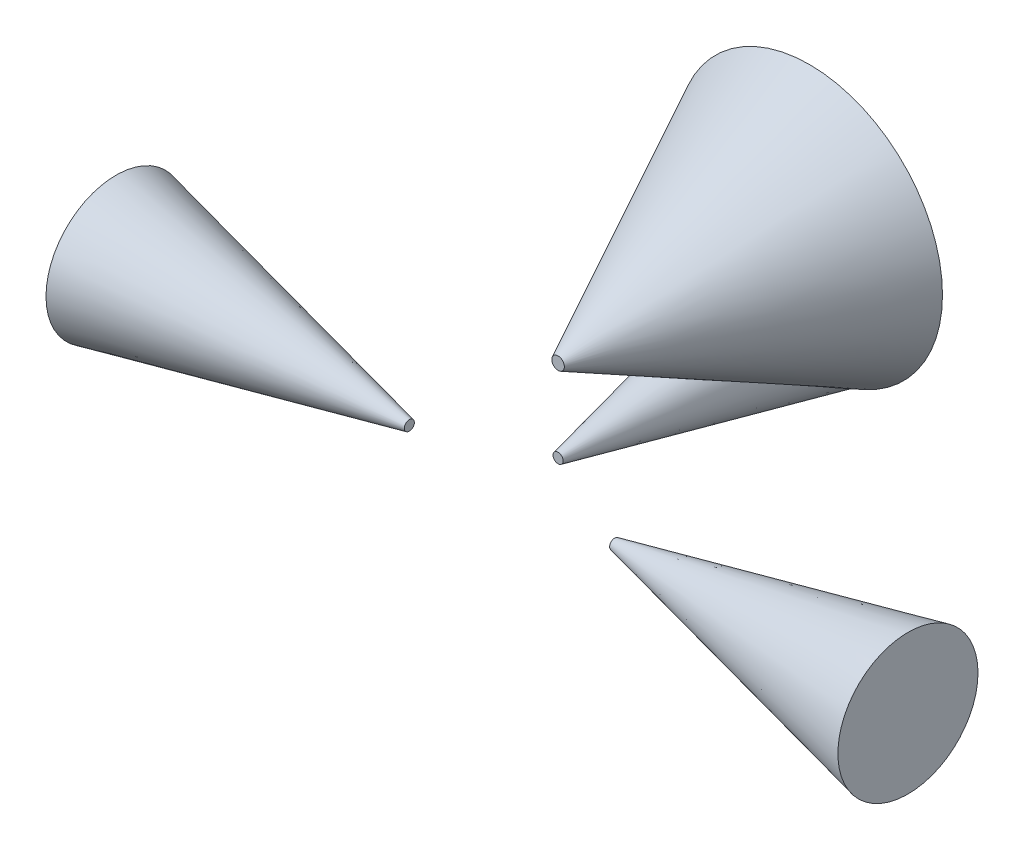
SolidWorks part; units mm, degrees
ref_plane "Front Plane" through (0, 0, 0) normal (0, 0, 1) x (1, 0, 0)
ref_plane "Top Plane" through (0, 0, 0) normal (0, 1, 0) x (1, 0, 0)
ref_plane "Right Plane" through (0, 0, 0) normal (1, 0, 0) x (0, 0, -1)
sketch "Sketch1" plane through (0, 0, 0) normal (0, 1, 0) x (1, 0, 0)
  line L0 (-14.5, 32) -> (-24.5, 32)
ref_plane "Plane1" through (-24.5, 0, -32) normal (-1, 0, 0) x (0, 0, 1)
sketch "Sketch3" plane through (-24.5, 0, -32) normal (-1, 0, 0) x (0, 0, 1)
  circle A0 centre (0, 9) radius 1.2
extrude "ToF Cone Left" add sketch "Sketch3" along normal blind 70 draft 12.5 separate body draft outward yes
sketch "Sketch4" plane through (0, 0, 0) normal (0, 1, 0) x (1, 0, 0)
  line L0 (0, 33) -> (0, 43)
ref_plane "Plane2" through (0, 0, -43) normal (0, 0, -1) x (-1, 0, 0)
sketch "Sketch6" plane through (0, 0, -43) normal (0, 0, -1) x (-1, 0, 0)
  circle A0 centre (0, 9) radius 1.2
extrude "ToF Cone Ahead" add sketch "Sketch6" along normal blind 70 draft 12.5 separate body draft outward yes
sketch "Sketch7" plane through (0, 0, 0) normal (0, 1, 0) x (1, 0, 0)
  line L0 (14.5, 32) -> (24.5, 32)
ref_plane "Plane3" through (24.5, 0, -32) normal (1, 0, 0) x (0, 0, -1)
sketch "Sketch9" plane through (24.5, 0, -32) normal (1, 0, 0) x (0, 0, -1)
  circle A0 centre (0, 9) radius 1.2
extrude "ToF Cone Right" add sketch "Sketch9" along normal blind 70 draft 12.5 separate body draft outward yes
sketch "Sketch10" plane through (0, 0, 0) normal (0, 1, 0) x (1, 0, 0)
  line L0 (0, 33) -> (0, 43)
ref_plane "Plane4" through (0, 0, -43) normal (0, 0, -1) x (-1, 0, 0)
sketch "Sketch12" plane through (0, 0, -43) normal (0, 0, -1) x (-1, 0, 0)
  circle A0 centre (0, 28.6) radius 1.5
extrude "Camera FOV (horizontal)" add sketch "Sketch12" along normal blind 60 draft 26.75 separate body draft outward yes
